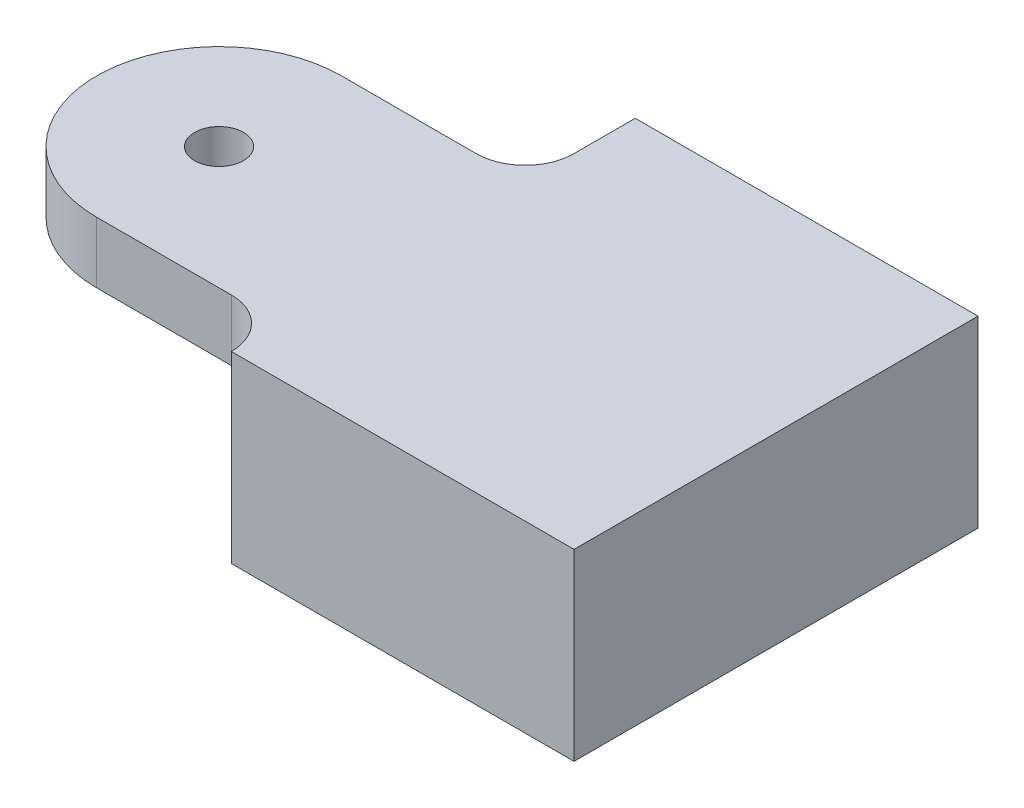
SolidWorks part; units mm, degrees
ref_plane "Ebene vorne" through (0, 0, 0) normal (0, 0, 1) x (1, 0, 0)
ref_plane "Ebene oben" through (0, 0, 0) normal (0, 1, 0) x (1, 0, 0)
ref_plane "Ebene rechts" through (0, 0, 0) normal (1, 0, 0) x (0, 0, -1)
sketch "Skizze2" plane through (0, 0, 0) normal (0, 1, 0) x (1, 0, 0)
  line L2 (-28, 33) -> (0, 33)
  line L4 (0, 0) -> (0, 33)
  line L5 (-43, 4) -> (-43, 24)
  line L6 (-43, 24) -> (-28, 24)
  line L7 (-28, 24) -> (-28, 33)
  line L8 (-43, 4) -> (-28, 4)
  line L9 (-28, 4) -> (-28, 0)
  line L10 (-28, 0) -> (0, 0)
  circle A0 centre (-43, 14) radius 10
  circle A1 centre (-43, 14) radius 2
  dimension "D1" = 20
  dimension "D2" = 4
  dimension "D3" = 9
  dimension "D4" = 28
  dimension "D5" = 4
  dimension "D6" = 15
  dimension "D7" = 15
  dimension "D8" = 28
extrude "Aufsatz-Linear austragen1" add sketch "Skizze2" along normal blind 5 contours A0 L8 L9 L10 L4 L2 L7 L6 | A1 L5 A0 | A1 L5 A0 region at (-16.4007, 0, -16.1651) region at (-38.6144, 0, -14) region at (-47.3856, 0, -14)
sketch "Skizze4" plane through (0, 0, 0) normal (0, -1, 0) x (1, 0, 0)
  line L0 (-28, -33) -> (-28, 0)
  line L1 (2.75, 0) -> (-2.75, 0) construction
  line L2 (-28, -4) -> (-28, 0) construction
  line L3 (-28, 0) -> (0, 0)
  line L4 (0, 0) -> (0, -33)
  line L5 (0, -2.75) -> (0, 2.75) construction
  line L6 (-28, -33) -> (0, -33) construction
  line L7 (0, -33) -> (-28, -33)
extrude "Aufsatz-Linear austragen3" add sketch "Skizze4" along normal blind 10
fillet "Verrundung1" radius 4 1 edges at (-28, 2.5, -4)
fillet "Verrundung2" radius 4 1 edges at (-28, 2.5, -24)
